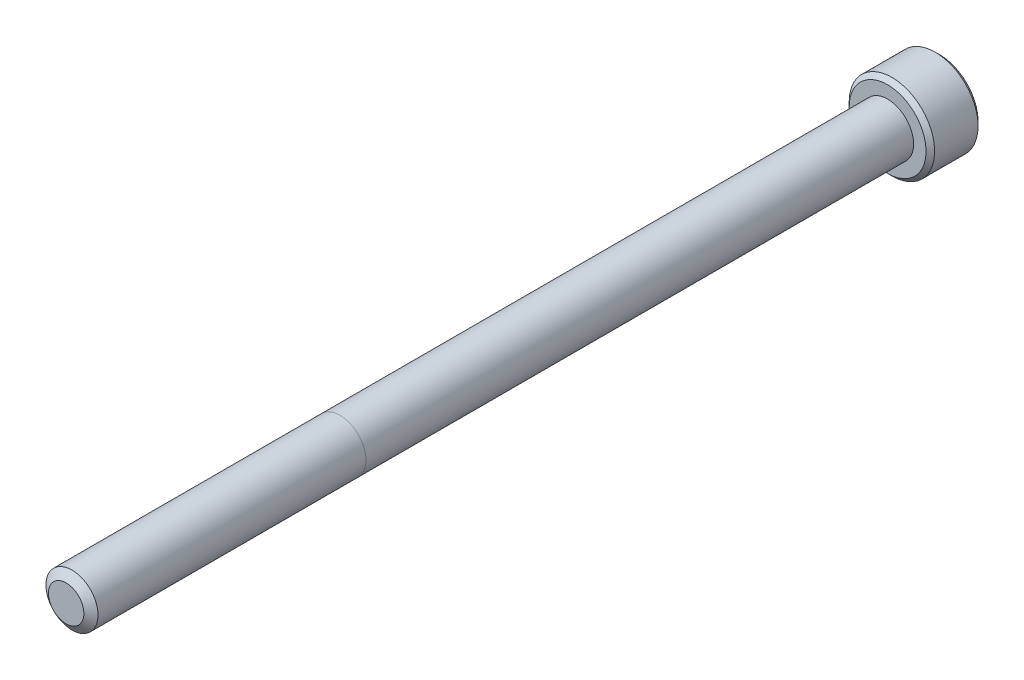
SolidWorks part; units mm, degrees
ref_plane "Front Plane" through (0, 0, 0) normal (0, 0, 1) x (1, 0, 0)
ref_plane "Top Plane" through (0, 0, 0) normal (0, 1, 0) x (1, 0, 0)
ref_plane "Right Plane" through (0, 0, 0) normal (1, 0, 0) x (0, 0, -1)
sketch "Sketch1" plane through (0, 0, 0) normal (0, 0, 1) x (1, 0, 0)
  circle A0 centre (0, 0) radius 2.413
  dimension "OD" = 4.826
extrude "Extrude1" add sketch "Sketch1" against normal blind 76.2
sketch "Sketch2" plane through (0, 0, 0) normal (0, 0, 1) x (1, 0, 0)
  circle A0 centre (0, 0) radius 2.413 construction
  circle A1 centre (0, 0) radius 2.413
curve "Helix/Spiral1" [suppressed] parameters "pitch"=0.7937
sketch "Sketch3" plane through (0, 0, 0) normal (1, 0, 0) x (0, 0, -1)
  line L0 (-0.6945, 2.413) -> (-0.3969, 1.8974)
  line L1 (-0.3969, 1.8974) -> (-0.2977, 1.8974)
  line L2 (-0.2977, 1.8974) -> (0, 2.413)
  line L3 (-0.6945, 2.413) -> (0, 2.413)
  line L4 (-0.3473, 2.413) -> (-0.3473, 1.8974) construction
  line L5 (-0.5457, 2.1552) -> (-0.1488, 2.1552) construction
  line L6 (0, 2.413) -> (0, -2.413) construction
  dimension "D2" = 0.3969
  dimension "D3" = 60
sweep "Cut-Sweep1" [suppressed] cut profiles "Sketch3" path "Helix/Spiral1"
sketch "Sketch4" plane through (0, 0, 0) normal (1, 0, 0) x (0, 0, -1)
  line L0 (0.5388, 2.413) -> (0, 1.6434)
  line L1 (0, 1.6434) -> (0, 2.413)
  line L2 (0.5388, 2.413) -> (0, 2.413)
  line L3 (-0.6945, 2.413) -> (0, 2.413) construction
  line L4 (0, 0) -> (7.0209, 0) construction
  dimension "D1" = 55
  dimension "D2" = 0.254
revolve "Cut-Revolve1" cut sketch "Sketch4" angle 360 about L4
sketch "Sketch5" [suppressed] plane through (0, 0, 0) normal (1, 0, 0) x (0, 0, -1)
  line L0 (50.8, -1.9083) -> (50.8, 1.7217) construction
  line L1 (50.8, 2.54) -> (25.5202, 2.54)
  line L2 (50.8, 2.54) -> (50.8, 0)
  line L3 (50.8, 0) -> (25.4, 0)
  line L4 (25.4, 2.2098) -> (25.4, 0)
  line L5 (25.5202, 2.54) -> (25.4, 2.2098)
  line L6 (0, 0) -> (9.9695, 0) construction
  point P3 (25.4, 2.54)
  point P10 (25.4, 2.54)
  dimension "D1" = 0.3302
  dimension "Thread min" = 25.4
  dimension "D2" = 0.127
  dimension "D3" = 20
revolve "partially thread" [suppressed] add sketch "Sketch5" angle 360 about L6
sketch "Sketch6" plane through (0, 0, -76.2) normal (0, 0, -1) x (-1, 0, 0)
  circle A0 centre (0, 0) radius 3.9624
  dimension "head dia" = 7.9248
extrude "Extrude2" add sketch "Sketch6" along normal blind 4.826
sketch "Sketch7" plane through (0, 0, -81.026) normal (0, 0, -1) x (-1, 0, 0)
  line L1 (0, 2.2914) -> (-1.9844, 1.1457)
  line L2 (-1.9844, 1.1457) -> (-1.9844, -1.1457)
  line L3 (-1.9844, -1.1457) -> (0, -2.2914)
  line L4 (0, -2.2914) -> (1.9844, -1.1457)
  line L5 (1.9844, -1.1457) -> (1.9844, 1.1457)
  line L6 (1.9844, 1.1457) -> (0, 2.2914)
  circle A0 centre (0, 0) radius 1.9844 construction
  dimension "hex dia" = 3.9688
extrude "Cut-Extrude1" cut sketch "Sketch7" against normal blind 2.9766
sketch "Sketch8" plane through (0, 0, -81.026) normal (0, 0, -1) x (-1, 0, 0)
  circle A0 centre (0, 0) radius 2.2914
extrude "Cut-Extrude2" cut sketch "Sketch8" against normal through all draft 45
chamfer "Chamfer1" distance 0.3962 angle 45 2 edges at (-3.9624, 0, -81.026) (-3.9624, 0, -76.2)
sketch "Sketch10" plane through (0, 0, 0) normal (0, 1, 0) x (1, 0, 0)
  line L0 (-2.413, 25.4) -> (2.413, 25.4)
  line L1 (-2.413, 76.2) -> (-2.413, 0.5388) construction
  line L2 (2.413, 0.5388) -> (2.413, 76.2) construction
  line L3 (-1.6434, 0) -> (1.6434, 0) construction
  dimension "D1" = 25.4
split line "Split Line2"
equation "\"D3@Helix/Spiral1\" = \"screw length@Extrude1\"+\"pitch@Helix/Spiral1\""
equation "\"D1@Sketch3\" = \"pitch@Helix/Spiral1\"*.125"
equation "\"D2@Sketch3\" = \"pitch@Helix/Spiral1\"*.5"
equation "\"D1@Cut-Extrude1\" = \"hex dia@Sketch7\"*.75"
equation "\"D1@Chamfer1\" = \"head dia@Sketch6\"*.05"
